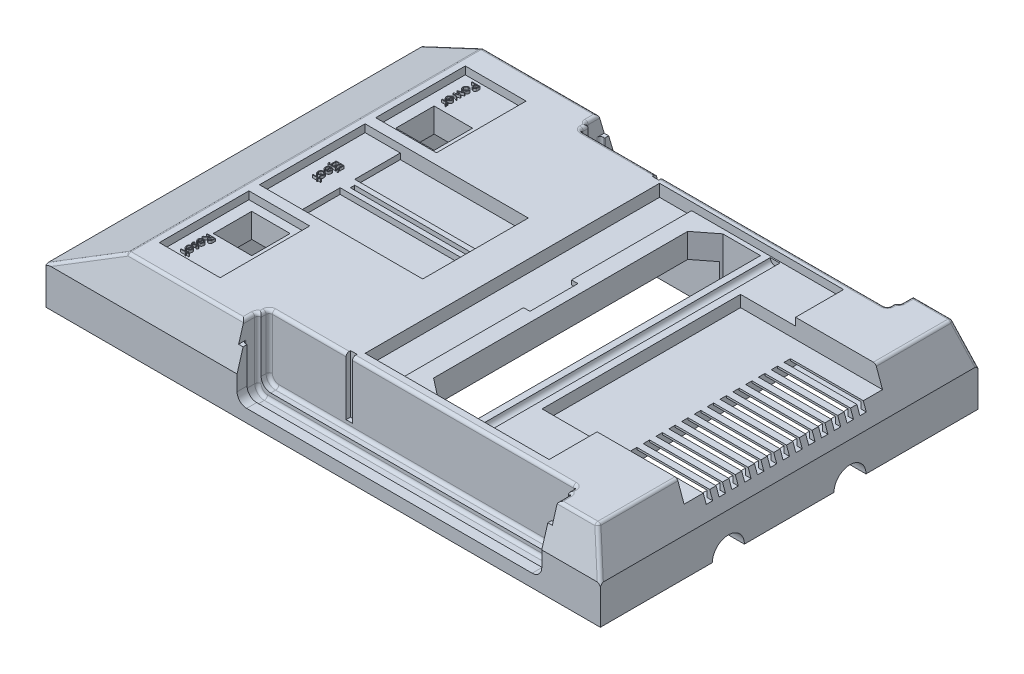
SolidWorks part; units mm, degrees
ref_plane "Front Plane" through (0, 0, 0) normal (0, 0, 1) x (1, 0, 0)
ref_plane "Top Plane" through (0, 0, 0) normal (0, 1, 0) x (1, 0, 0)
ref_plane "Right Plane" through (0, 0, 0) normal (1, 0, 0) x (0, 0, -1)
sketch "Sketch1" plane through (0, 0, 0) normal (0, 1, 0) x (1, 0, 0)
  line L1 (-219.964, -149.86) -> (0, -149.86)
  line L2 (-219.964, -149.86) -> (-219.964, 0)
  line L3 (-219.964, 0) -> (0, 0)
  line L4 (0, -149.86) -> (0, 0)
  dimension "D1" = 149.86
  dimension "D2" = 219.964
ref_plane "MiddleTop" through (0, 14.986, 0) normal (0, 1, 0) x (1, 0, 0)
sketch "Sketch2" plane through (0, 14.986, 0) normal (0, 1, 0) x (1, 0, 0)
  line L1 (0, 0) -> (-219.964, 0)
  line L2 (0, 0) -> (0, -149.86)
  line L3 (0, -149.86) -> (-219.964, -149.86)
  line L4 (-219.964, 0) -> (-219.964, -149.86)
extrude "Boss-Extrude1" add sketch "Sketch1" along normal blind 14.986
ref_plane "Plane2" through (0, 30.48, 0) normal (0, 1, 0) x (1, 0, 0)
sketch "Sketch3" plane through (0, 30.48, 0) normal (0, 1, 0) x (1, 0, 0)
  line L0 (0, -149.86) -> (-219.964, -149.86) construction
  line L1 (-192.024, -4.572) -> (-5.588, -4.572)
  line L2 (-192.024, -4.572) -> (-192.024, -145.288)
  line L3 (-192.024, -145.288) -> (-5.588, -145.288)
  line L4 (-5.588, -4.572) -> (-5.588, -145.288)
  line L5 (-219.964, 0) -> (-219.964, -149.86) construction
  line L6 (0, 0) -> (0, -149.86) construction
  dimension "D1" = 140.716
  dimension "D2" = 4.572
  dimension "D3" = 27.94
  dimension "D4" = 5.588
loft "Loft1" add profiles "Sketch2", "Sketch3" connector at (-219.964, 14.986, 149.86) connector at (-192.024, 30.48, 145.288)
sketch "Sketch4" plane through (0, 30.48, 0) normal (0, 1, 0) x (1, 0, 0)
  line L0 (-192.024, -145.288) -> (-5.588, -145.288) construction
  line L1 (-189.23, -135.636) -> (-165.1, -135.636)
  line L2 (-189.23, -135.636) -> (-189.23, -100.076)
  line L3 (-189.23, -100.076) -> (-165.1, -100.076)
  line L4 (-165.1, -135.636) -> (-165.1, -100.076)
  line L5 (-192.024, -4.572) -> (-192.024, -145.288) construction
  line L6 (-5.588, -4.572) -> (-192.024, -4.572) construction
  line L7 (-189.23, -49.784) -> (-165.1, -49.784)
  line L8 (-189.23, -49.784) -> (-189.23, -14.224)
  line L9 (-189.23, -14.224) -> (-165.1, -14.224)
  line L10 (-165.1, -49.784) -> (-165.1, -14.224)
  point P12 (-177.165, -14.224)
  dimension "D1" = 35.56
  dimension "D2" = 24.13
  dimension "D3" = 9.652
  dimension "D4" = 2.794
  dimension "D5" = 24.13
  dimension "D6" = 35.56
  dimension "D7" = 2.794
  dimension "D8" = 9.652
sketch "Sketch5" plane through (0, 30.48, 0) normal (0, 1, 0) x (1, 0, 0)
  line L0 (-189.23, -100.076) -> (-165.1, -100.076) construction
  line L1 (-189.23, -95.885) -> (-124.46, -95.885)
  line L2 (-189.23, -95.885) -> (-189.23, -53.975)
  line L3 (-189.23, -53.975) -> (-124.46, -53.975)
  line L4 (-124.46, -95.885) -> (-124.46, -53.975)
  line L5 (-192.024, -4.572) -> (-192.024, -145.288) construction
  dimension "D1" = 41.91
  dimension "D2" = 4.191
  dimension "D3" = 2.794
  dimension "D4" = 64.77
extrude "Cut-Extrude1" cut sketch "Sketch4" against normal blind 3.048
extrude "Cut-Extrude2" cut sketch "Sketch5" against normal blind 3.048
ref_plane "Plane3" through (0, 25.146, 0) normal (0, 1, 0) x (1, 0, 0)
sketch "Sketch6" plane through (0, 25.146, 0) normal (0, 1, 0) x (1, 0, 0)
  line L0 (-189.23, -53.975) -> (-189.23, -95.885) construction
  line L1 (-175.26, -72.0598) -> (-124.46, -72.0598)
  line L2 (-175.26, -72.0598) -> (-175.26, -77.851)
  line L3 (-175.26, -77.851) -> (-124.46, -77.851)
  line L4 (-124.46, -72.0598) -> (-124.46, -77.851)
  line L5 (-189.23, -95.885) -> (-124.46, -95.885) construction
  dimension "D1" = 50.8
  dimension "D2" = 13.97
  dimension "D3" = 5.7912
  dimension "D4" = 18.034
sketch "Sketch10" plane through (0, 30.48, 0) normal (0, 1, 0) x (1, 0, 0)
  line L6 (-219.964, -149.86) -> (0, -149.86) construction
  line L9 (-144.145, -145.8976) -> (-145.923, -145.8976)
  line L10 (-145.923, -145.8976) -> (-145.923, -139.8016)
  line L11 (-145.923, -139.8016) -> (-144.653, -139.8016)
  line L12 (-144.653, -139.8016) -> (-144.653, -136.5758)
  line L13 (-144.653, -136.5758) -> (-22.733, -136.5758)
  line L14 (-22.733, -136.5758) -> (-22.733, -139.8016)
  line L15 (-22.733, -139.8016) -> (-21.463, -139.8016)
  line L16 (-21.463, -139.8016) -> (-21.463, -145.8976)
  line L17 (-21.463, -145.8976) -> (-23.241, -145.8976)
  line L21 (-23.241, -149.86) -> (-144.145, -149.86)
  line L22 (-144.145, -145.8976) -> (-144.145, -149.86)
  line L23 (-23.241, -145.8976) -> (-23.241, -149.86)
  line L24 (0, -149.86) -> (0, 0) construction
  line L25 (-219.964, -74.93) -> (-5.588, -74.93) construction
  line L27 (-219.964, 0) -> (-219.964, -149.86) construction
  line L28 (-5.588, -145.288) -> (-5.588, -4.572) construction
  line L29 (-21.463, -3.9624) -> (-23.241, -3.9624)
  line L30 (-21.463, -10.0584) -> (-21.463, -3.9624)
  line L31 (-22.733, -10.0584) -> (-21.463, -10.0584)
  line L32 (-22.733, -13.2842) -> (-22.733, -10.0584)
  line L33 (-144.653, -13.2842) -> (-22.733, -13.2842)
  line L34 (-144.653, -10.0584) -> (-144.653, -13.2842)
  line L35 (-145.923, -10.0584) -> (-144.653, -10.0584)
  line L36 (-145.923, -3.9624) -> (-145.923, -10.0584)
  line L37 (-144.145, -3.9624) -> (-145.923, -3.9624)
  line L38 (-144.145, -3.9624) -> (-144.145, 0)
  line L39 (-23.241, 0) -> (-144.145, 0)
  line L40 (-23.241, -3.9624) -> (-23.241, 0)
  dimension "D1" = 13.2842
  dimension "D2" = 6.096
  dimension "D3" = 3.2258
  dimension "D4" = 1.27
  dimension "D5" = 124.46
  dimension "D6" = 3.2258
  dimension "D7" = 1.27
  dimension "D8" = 1.778
  dimension "D9" = 6.096
  dimension "D10" = 21.463
  dimension "D11" = 1.778
sketch "Sketch12" plane through (0, 30.48, 0) normal (0, 1, 0) x (1, 0, 0)
  line L1 (-145.923, -10.0584) -> (-21.463, -10.0584)
  line L2 (-145.923, -10.0584) -> (-145.923, -3.9624)
  line L3 (-145.923, -3.9624) -> (-21.463, -3.9624)
  line L4 (-21.463, -10.0584) -> (-21.463, -3.9624)
  line L5 (-145.923, -145.8976) -> (-21.463, -145.8976)
  line L6 (-145.923, -145.8976) -> (-145.923, -139.8016)
  line L7 (-145.923, -139.8016) -> (-21.463, -139.8016)
  line L8 (-21.463, -145.8976) -> (-21.463, -139.8016)
extrude "Cut-Extrude4" cut sketch "Sketch12" against normal blind 27.94
extrude "Cut-Extrude5" cut sketch "Sketch10" against normal blind 25.4
sketch "Sketch14" plane through (0, 30.48, 0) normal (0, 1, 0) x (1, 0, 0)
  line L1 (-145.923, -145.1356) -> (-144.145, -145.1356)
  line L2 (-145.923, -145.1356) -> (-145.923, -149.86)
  line L3 (-145.923, -149.86) -> (-144.145, -149.86)
  line L4 (-144.145, -145.1356) -> (-144.145, -149.86)
  line L5 (-21.463, -145.8976) -> (-23.241, -145.8976)
  line L6 (-21.463, -145.8976) -> (-21.463, -149.86)
  line L7 (-21.463, -149.86) -> (-23.241, -149.86)
  line L8 (-23.241, -145.8976) -> (-23.241, -149.86)
  line L9 (-145.923, -4.7244) -> (-144.145, -4.7244)
  line L10 (-145.923, -4.7244) -> (-145.923, 0)
  line L11 (-145.923, 0) -> (-144.145, 0)
  line L12 (-144.145, -4.7244) -> (-144.145, 0)
  line L13 (-21.463, -3.9624) -> (-23.241, -3.9624)
  line L14 (-21.463, -3.9624) -> (-21.463, 0)
  line L15 (-21.463, 0) -> (-23.241, 0)
  line L16 (-23.241, -3.9624) -> (-23.241, 0)
  dimension "D1" = 4.7244
  dimension "D2" = 4.7244
  dimension "D3" = 1.778
  dimension "D4" = 1.778
extrude "Cut-Extrude6" cut sketch "Sketch14" against normal blind 7.366
sketch "Sketch15" plane through (0, 30.48, 0) normal (0, 1, 0) x (1, 0, 0)
  line L0 (-5.588, -145.288) -> (-5.588, -4.572) construction
  line L1 (-110.363, -16.002) -> (-37.338, -16.002)
  line L2 (-110.363, -16.002) -> (-110.363, -132.842)
  line L3 (-110.363, -132.842) -> (-37.338, -132.842)
  line L4 (-37.338, -16.002) -> (-37.338, -35.052)
  line L5 (-5.588, -4.572) -> (-21.463, -4.572) construction
  line L6 (-37.338, -35.052) -> (-59.182, -35.052)
  line L7 (-59.182, -35.052) -> (-59.182, -113.792)
  line L8 (-59.182, -113.792) -> (-37.338, -113.792)
  line L9 (-37.338, -113.792) -> (-37.338, -132.842)
  dimension "D1" = 73.025
  dimension "D2" = 31.75
  dimension "D3" = 116.84
  dimension "D4" = 11.43
  dimension "D5" = 21.844
  dimension "D6" = 78.74
  dimension "D7" = 19.05
extrude "Cut-Extrude7" cut sketch "Sketch15" against normal blind 3.048
sketch "Sketch16" plane through (0, 30.48, 0) normal (0, 1, 0) x (1, 0, 0)
  line L1 (-59.182, -35.052) -> (0.508, -35.052)
  line L2 (-59.182, -35.052) -> (-59.182, -113.792)
  line L3 (-59.182, -113.792) -> (0.508, -113.792)
  line L4 (0.508, -35.052) -> (0.508, -113.792)
  dimension "D1" = 59.69
extrude "Cut-Extrude8" cut sketch "Sketch16" against normal blind 7.62
sketch "Sketch17" plane through (0, 30.48, 0) normal (0, 1, 0) x (1, 0, 0)
  line L0 (-110.363, -132.842) -> (-37.338, -132.842) construction
  line L1 (-110.363, -16.002) -> (-97.663, -16.002)
  line L2 (-110.363, -16.002) -> (-110.363, -132.842)
  line L3 (-110.363, -132.842) -> (-97.663, -132.842)
  line L4 (-97.663, -16.002) -> (-97.663, -63.627)
  line L5 (-97.663, -63.627) -> (-95.123, -63.627)
  line L6 (-95.123, -63.627) -> (-95.123, -82.677)
  line L7 (-95.123, -82.677) -> (-97.663, -82.677)
  line L8 (-97.663, -82.677) -> (-97.663, -132.842)
  dimension "D1" = 12.7
  dimension "D2" = 19.05
  dimension "D3" = 47.625
  dimension "D4" = 2.54
extrude "Cut-Extrude9" cut sketch "Sketch17" against normal blind 4.826
sketch "Sketch18" plane through (0, 30.48, 0) normal (0, 1, 0) x (1, 0, 0)
  line L0 (-83.5048, -17.78) -> (-91.313, -23.876)
  line L1 (-83.5048, -17.78) -> (-68.5188, -17.78)
  line L2 (-91.313, -23.876) -> (-91.313, -124.714)
  line L3 (-83.5048, -130.81) -> (-68.5188, -130.81)
  line L4 (-68.5188, -17.78) -> (-68.5188, -130.81)
  line L5 (-83.5048, -130.81) -> (-91.313, -124.714)
  line L6 (-97.663, -132.842) -> (-37.338, -132.842) construction
  line L8 (-95.123, -82.677) -> (-95.123, -63.627) construction
  dimension "D1" = 14.986
  dimension "D2" = 9.906
  dimension "D3" = 9.906
  dimension "D4" = 14.986
  dimension "D5" = 100.838
  dimension "D6" = 113.03
  dimension "D7" = 2.032
  dimension "D8" = 3.81
extrude "Cut-Extrude10" cut sketch "Sketch18" against normal through all
sketch "Sketch19" plane through (0, 30.48, 0) normal (0, 1, 0) x (1, 0, 0)
  line L0 (0, -149.86) -> (0, 0) construction
  line L1 (-31.75, -42.672) -> (0, -42.672)
  line L2 (-31.75, -42.672) -> (-31.75, -45.212)
  line L3 (-31.75, -45.212) -> (0, -45.212)
  line L4 (0, -42.672) -> (0, -45.212)
  line L5 (-2.8398, -35.052) -> (-59.182, -35.052) construction
  dimension "D1" = 2.54
  dimension "D2" = 31.75
  dimension "D3" = 7.62
extrude "Cut-Extrude11" cut sketch "Sketch19" against normal blind 10.922
pattern_linear "LPattern1" count 13 spacing 5.08 along (0, 0, 1) of "Cut-Extrude11"
ref_plane "Plane5" through (0, 0, 103.632) normal (0, 0, 1) x (1, 0, 0)
sketch "Sketch20" plane through (0, 0, 103.632) normal (0, 0, 1) x (1, 0, 0)
  line L0 (-2.8398, 22.86) -> (-31.75, 22.86) construction
  line L1 (-31.75, 22.098) -> (-3.81, 22.098)
  line L2 (-31.75, 22.098) -> (-31.75, 19.558)
  line L3 (-31.75, 19.558) -> (-3.81, 19.558)
  line L4 (-3.81, 22.098) -> (-3.81, 19.558)
  line L6 (-31.75, 19.558) -> (-31.75, 22.86) construction
  dimension "D1" = 0.762
  dimension "D2" = 2.54
  dimension "D3" = 0
  dimension "D4" = 27.94
extrude "Cut-Extrude12" cut sketch "Sketch20" against normal blind 63.5
sketch "Sketch25" plane through (0, 30.48, 0) normal (0, 1, 0) x (1, 0, 0)
  line L1 (-175.26, -72.0598) -> (-124.46, -72.0598)
  line L2 (-175.26, -72.0598) -> (-175.26, -53.975)
  line L3 (-175.26, -53.975) -> (-124.46, -53.975)
  line L4 (-124.46, -72.0598) -> (-124.46, -53.975)
  line L5 (-175.26, -77.851) -> (-124.46, -77.851)
  line L6 (-175.26, -77.851) -> (-175.26, -95.885)
  line L7 (-175.26, -95.885) -> (-124.46, -95.885)
  line L8 (-124.46, -77.851) -> (-124.46, -95.885)
extrude "Cut-Extrude14" cut sketch "Sketch25" against normal blind 5.334
sketch "Sketch21" plane through (0, 30.48, 0) normal (0, 1, 0) x (1, 0, 0)
  line L1 (-173.228, -74.0918) -> (-126.238, -74.0918)
  line L2 (-173.228, -74.0918) -> (-173.228, -75.819)
  line L3 (-173.228, -75.819) -> (-126.238, -75.819)
  line L4 (-126.238, -74.0918) -> (-126.238, -75.819)
  line L7 (-124.46, -53.975) -> (-189.23, -53.975) construction
  line L8 (-175.26, -95.885) -> (-124.46, -95.885) construction
  line L9 (-124.46, -95.885) -> (-124.46, -53.975) construction
  dimension "D1" = 20.1168
  dimension "D2" = 20.066
  dimension "D3" = 46.99
  dimension "D4" = 1.778
extrude "Cut-Extrude13" cut sketch "Sketch21" against normal through all
ref_plane "Plane6" through (0, 0, 16.51) normal (0, 0, 1) x (1, 0, 0)
sketch "Sketch26" plane through (0, 0, 16.51) normal (0, 0, 1) x (1, 0, 0)
  line L2 (-37.338, 27.432) -> (-97.663, 27.432) construction
  circle A0 centre (-64.008, 27.432) radius 1.905
  dimension "D3" = 3.81
  dimension "D1" = 0
  dimension "D2" = 58.42
extrude "Cut-Extrude15" cut sketch "Sketch26" along normal blind 115.57
fillet "Fillet1" radius 3.81 12 edges at (-144.145, 5.08, 1.9812) (-23.241, 5.08, 1.9812) (-144.145, 5.08, 147.8788) (-23.241, 5.08, 147.8788) (-22.733, 5.08, 138.1887) (-144.653, 5.08, 138.1887) (-144.653, 5.08, 11.6713) (-22.733, 5.08, 11.6713) (-21.463, 2.54, 142.8496) (-145.923, 2.54, 142.8496) (-145.923, 2.54, 7.0104) (-21.463, 2.54, 7.0104)
fillet "Fillet2" radius 1.27 30 edges at (-145.923, 14.732, 3.9624) (-144.8071, 3.6559, 3.9624) (-83.693, 2.54, 3.9624) (-22.5789, 3.6559, 3.9624) (-21.463, 18.415, 10.0584) (-145.923, 18.415, 10.0584) (-144.8071, 3.6559, 10.0584) (-83.693, 2.54, 10.0584) (-22.733, 19.685, 13.2842) (-144.653, 19.685, 13.2842) (-143.5371, 6.1959, 13.2842) (-83.693, 5.08, 13.2842) (-22.733, 19.685, 136.5758) (-23.8489, 6.1959, 136.5758) (-144.653, 19.685, 136.5758) (-143.5371, 6.1959, 136.5758) (-21.463, 18.415, 139.8016) (-22.5789, 3.6559, 139.8016) (-83.693, 2.54, 139.8016) (-144.8071, 3.6559, 139.8016) (-21.463, 14.732, 145.8976) (-22.5789, 3.6559, 145.8976) (-83.693, 2.54, 145.8976) (-144.8071, 3.6559, 145.8976) (-21.463, 14.732, 3.9624) (-22.5789, 3.6559, 10.0584) (-23.8489, 6.1959, 13.2842) (-83.693, 5.08, 136.5758) (-145.923, 18.415, 139.8016) (-145.923, 14.732, 145.8976)
fillet "Fillet3" radius 1.27 29 edges at (-21.835, 30.48, 140.1736) (-21.835, 30.48, 9.6864) (-145.551, 30.48, 9.6864) (-145.551, 30.48, 140.1736) (-144.653, 30.48, 11.0363) (-144.281, 30.48, 12.9122) (-22.733, 30.48, 11.0363) (-23.105, 30.48, 12.9122) (-22.733, 30.48, 138.8237) (-23.105, 30.48, 136.9478) (-144.653, 30.48, 138.8237) (-144.281, 30.48, 136.9478) (-83.693, 30.48, 13.2842) (-83.693, 30.48, 136.5758)
sketch "Sketch27" plane through (0, 30.48, 0) normal (0, 1, 0) x (1, 0, 0)
  line L0 (-140.843, -136.5758) -> (-26.543, -136.5758) construction
  line L1 (-114.173, -134.7978) -> (-111.633, -134.7978)
  line L2 (-114.173, -134.7978) -> (-114.173, -136.5758)
  line L3 (-114.173, -136.5758) -> (-111.633, -136.5758)
  line L4 (-111.633, -134.7978) -> (-111.633, -136.5758)
  line L5 (-145.923, -144.6276) -> (-145.923, -141.0716) construction
  line L6 (0, -74.93) -> (-226.7454, -74.93) construction
  line L8 (0, -148.663) -> (0, -1.197) construction
  dimension "D1" = 1.778
  dimension "D2" = 2.54
  dimension "D3" = 31.75
sketch "Sketch28" plane through (0, 30.48, 0) normal (0, 1, 0) x (1, 0, 0)
  line L2 (-114.173, -13.2842) -> (-114.173, -15.0622)
  line L3 (-114.173, -15.0622) -> (-111.633, -15.0622)
  line L4 (-111.633, -13.2842) -> (-111.633, -15.0622)
  line L5 (-145.923, -4.1972) -> (-145.923, -8.7884) construction
  line L8 (-114.173, -13.2842) -> (-111.633, -13.2842)
  line L9 (-143.383, -13.2842) -> (-24.003, -13.2842) construction
  dimension "D1" = 1.778
  dimension "D2" = 2.54
  dimension "D3" = 31.75
  dimension "D4" = 0
extrude "Cut-Extrude16" cut sketch "Sketch27" against normal blind 22.86
extrude "Cut-Extrude17" cut sketch "Sketch28" against normal blind 22.86
sketch "Sketch29" plane through (0, 0, 0) normal (0, 1, 0) x (1, 0, 0)
  line L0 (-191.6954, -5.5214) -> (-191.6954, -144.3386) construction
  line L1 (-190.4254, -18.3642) -> (-7.5454, -18.3642)
  line L2 (-190.4254, -18.3642) -> (-190.4254, -132.6642)
  line L3 (-190.4254, -132.6642) -> (-7.5454, -132.6642)
  line L4 (-7.5454, -18.3642) -> (-7.5454, -132.6642)
  line L5 (-24.003, -14.5542) -> (-111.633, -14.5542) construction
  dimension "D1" = 114.3
  dimension "D2" = 182.88
  dimension "D3" = 1.27
  dimension "D4" = 3.81
extrude "Cut-Extrude18" cut sketch "Sketch29" along normal blind 17.78
sketch "Sketch30" plane through (0, 30.48, 0) normal (0, 1, 0) x (1, 0, 0)
  line L1 (-184.6913, -46.355) -> (-169.4513, -46.355)
  line L2 (-184.6913, -46.355) -> (-184.6913, -31.115)
  line L3 (-184.6913, -31.115) -> (-169.4513, -31.115)
  line L4 (-169.4513, -46.355) -> (-169.4513, -31.115)
  line L5 (-124.46, -53.975) -> (-189.23, -53.975) construction
  line L6 (-192.3113, -144.3386) -> (-192.3113, -5.5214) construction
  line L7 (0, -74.93) -> (-237.3505, -74.93) construction
  line L8 (0, -148.663) -> (0, -1.197) construction
  line L9 (-184.6913, -118.745) -> (-169.4513, -118.745)
  line L10 (-169.4513, -103.505) -> (-169.4513, -118.745)
  line L11 (-184.6913, -103.505) -> (-169.4513, -103.505)
  line L12 (-184.6913, -103.505) -> (-184.6913, -118.745)
  dimension "D1" = 15.24
  dimension "D2" = 15.24
  dimension "D3" = 7.62
  dimension "D4" = 7.62
extrude "Cut-Extrude19" cut sketch "Sketch30" against normal through all
ref_plane "Plane7" through (0, 27.432, 0) normal (0, 1, 0) x (1, 0, 0)
sketch "Sketch31" plane through (0, 27.432, 0) normal (0, 1, 0) x (1, 0, 0)
  line L0 (-184.4444, -29.1684) -> (-184.4444, -14.224) construction
  line L1 (-165.1, -14.224) -> (-189.23, -14.224) construction
  line L2 (-184.7529, -120.6295) -> (-184.7529, -133.3206) construction
  line L3 (-184.2212, -70.0663) -> (-184.2212, -81.9385) construction
  text T0 "Power"
  text T1 "Reset"
  text T2 "Eject"
extrude "Boss-Extrude2" add sketch "Sketch31" along normal blind 1.016
sketch "Sketch32" plane through (0, 0, 0) normal (0, 1, 0) x (1, 0, 0)
  line L0 (-31.75, -106.172) -> (-2.8398, -106.172) construction
  line L1 (-31.75, -42.672) -> (-6.35, -42.672)
  line L2 (-31.75, -42.672) -> (-31.75, -106.172)
  line L3 (-31.75, -106.172) -> (-6.35, -106.172)
  line L4 (-6.35, -42.672) -> (-6.35, -106.172)
  dimension "D1" = 25.4
extrude "Cut-Extrude20" cut sketch "Sketch32" along normal blind 20.32
sketch "Sketch33" plane through (0, 0, 0) normal (1, 0, 0) x (0, 0, -1)
  line L0 (82.4231, 0) -> (-82.4231, 0) construction
  circle A0 centre (-99.06, 0) radius 6.35
  circle A1 centre (-50.8, 0) radius 6.35
  dimension "D3" = 12.7
  dimension "D4" = 12.7
  dimension "D1" = 50.8
  dimension "D2" = 50.8
extrude "Cut-Extrude21" cut sketch "Sketch33" against normal blind 19.05
